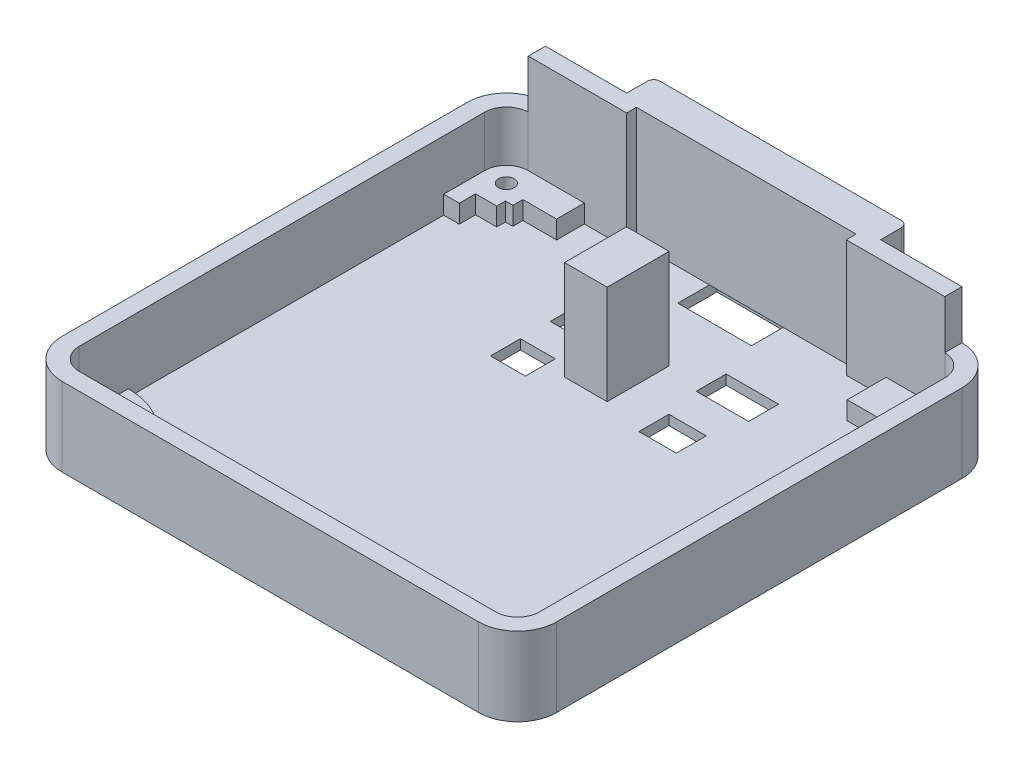
SolidWorks part; units mm, degrees
ref_plane "Front Plane" through (0, 0, 0) normal (0, 0, 1) x (1, 0, 0)
ref_plane "Top Plane" through (0, 0, 0) normal (0, 1, 0) x (1, 0, 0)
ref_plane "Right Plane" through (0, 0, 0) normal (1, 0, 0) x (0, 0, -1)
sketch "Sketch2" plane through (0, 0, 0) normal (0, 1, 0) x (1, 0, 0)
  line L6 (-46.8585, -41.275) -> (-46.8585, 41.275)
  line L8 (46.8585, -41.275) -> (46.8585, 41.275)
  line L9 (42.418, -45.7155) -> (-42.418, -45.7155)
  line L10 (-42.418, 45.7155) -> (-16.8754, 45.7155)
  line L11 (-46.8585, -41.275) -> (-50.3585, -41.275)
  line L14 (-50.3585, -41.275) -> (-50.3585, 41.275)
  line L15 (-42.418, 45.7155) -> (-42.418, 49.2155)
  line L16 (-42.418, 41.275) -> (-37.8452, 38.0373)
  line L17 (-42.418, 49.2155) -> (42.418, 49.2155)
  line L18 (-37.8452, 38.0373) -> (-37.8452, 40.0693)
  line L19 (-37.8452, 40.0693) -> (-30.9872, 40.0693)
  line L20 (-30.9872, 40.0693) -> (-30.9872, 45.7155)
  line L21 (-37.8452, 38.0373) -> (-39.3692, 38.0373)
  line L22 (46.8585, 41.275) -> (50.3585, 41.275)
  line L23 (42.418, -45.7155) -> (42.418, -49.2155)
  line L24 (-39.3692, 38.0373) -> (-39.3692, 36.2593)
  line L25 (42.418, -49.2155) -> (-42.418, -49.2155)
  line L26 (-39.3692, 36.2593) -> (-43.6872, 36.2593)
  line L27 (-43.6872, 36.2593) -> (-43.6872, 32.9573)
  line L28 (50.3585, 41.275) -> (50.3585, -41.275)
  line L34 (-43.6872, 32.9573) -> (-46.8585, 32.9573)
  line L37 (42.418, 41.275) -> (50.0148, 49.9834)
  line L46 (-16.2544, 31.1733) -> (-10.1584, 31.1733)
  line L52 (-10.1584, 31.1733) -> (-10.1584, 25.0773)
  line L58 (-10.1584, 25.0773) -> (-17.2704, 25.0773)
  line L64 (-17.2704, 25.0773) -> (-17.2704, 31.1733)
  line L70 (-17.2704, 31.1733) -> (-16.2544, 31.1733)
  line L76 (-17.2704, 25.0773) -> (-17.2704, 18.9813)
  line L82 (-17.2704, 18.9813) -> (-10.1584, 18.9813)
  line L88 (-10.1584, 18.9813) -> (-10.1584, 12.8853)
  line L94 (-10.1584, 12.8853) -> (-17.2704, 12.8853)
  line L100 (-17.2704, 12.8853) -> (-17.2704, 18.9813)
  line L111 (22.418, 45.7155) -> (42.418, 45.7155)
  line L112 (-10.1584, 31.1733) -> (9.9076, 31.1733)
  line L113 (9.9076, 31.1733) -> (9.9076, 33.7133)
  line L114 (9.9076, 33.7133) -> (20.5756, 33.7133)
  line L115 (20.5756, 33.7133) -> (20.5756, 27.6173)
  line L116 (20.5756, 27.6173) -> (9.9076, 27.6173)
  line L117 (9.9076, 27.6173) -> (9.9076, 31.1733)
  line L118 (9.9076, 27.6173) -> (9.9076, 20.7633)
  line L119 (9.9076, 20.7633) -> (18.7976, 20.7633)
  line L120 (18.7976, 20.7633) -> (18.7976, 14.6673)
  line L121 (18.7976, 14.6673) -> (11.1776, 14.6673)
  line L122 (11.1776, 14.6673) -> (11.1776, 20.7633)
  line L123 (42.418, 41.275) -> (0, 41.275)
  line L124 (42.418, 41.275) -> (39.3704, 37.7815)
  line L125 (39.3704, 37.7815) -> (39.3704, 33.2095)
  line L126 (39.3704, 37.7815) -> (30.4804, 37.7815)
  line L127 (30.4804, 37.7815) -> (30.4804, 45.7155)
  line L128 (39.3704, 33.2095) -> (46.8585, 33.2095)
  line L129 (22.418, 45.7155) -> (-16.8754, 45.7155)
  line L130 (46.8585, -41.275) -> (46.8585, -31.275)
  line L131 (42.418, -45.7155) -> (32.418, -45.7155)
  line L132 (-42.418, -45.7155) -> (-32.418, -45.7155)
  line L133 (-46.8585, -41.275) -> (-46.8585, -31.275)
  arc A0 (-42.418, 45.7155) -> (-46.8585, 41.275) centre (-42.418, 41.275) ccw
  arc A1 (42.418, 45.7155) -> (46.8585, 41.275) centre (42.418, 41.275) cw
  arc A2 (-46.8585, -41.275) -> (-42.418, -45.7155) centre (-42.418, -41.275) ccw
  arc A3 (46.8585, -41.275) -> (42.418, -45.7155) centre (42.418, -41.275) cw
  circle A4 centre (42.418, 41.275) radius 1.6
  circle A5 centre (-42.418, 41.275) radius 1.6
  circle A6 centre (-42.418, -41.275) radius 1.6
  circle A7 centre (42.418, -41.275) radius 1.6
  arc A8 (-42.418, 49.2155) -> (-50.3585, 41.275) centre (-42.418, 41.275) ccw
  arc A9 (42.418, 49.2155) -> (50.3585, 41.275) centre (42.418, 41.275) cw
  arc A10 (42.418, -49.2155) -> (50.3585, -41.275) centre (42.418, -41.275) ccw
  arc A11 (-42.418, -49.2155) -> (-50.3585, -41.275) centre (-42.418, -41.275) cw
  arc A12 (46.8585, -31.275) -> (32.418, -45.7155) centre (46.8585, -45.7155) ccw
  arc A13 (-46.8585, -31.275) -> (-32.418, -45.7155) centre (-46.8585, -45.7155) cw
extrude "Boss-Extrude1" add sketch "Sketch2" along normal blind 1.5 contours L8 A12 L9 A3 A7 | A13 L6 A2 L9 A6 region at (-40.4967, 0, 39.3537) region at (40.4967, 0, 39.3537)
sketch "Sketch5" plane through (0, 0, 0) normal (0, -1, 0) x (1, 0, 0)
  line L0 (-17.2704, -25.0773) -> (-17.2704, -18.9813) construction
  line L1 (42.418, -41.275) -> (50.0148, -49.9834) construction
  line L2 (42.418, -41.275) -> (0, -41.275) construction
  line L3 (42.418, -41.275) -> (39.3704, -37.7815) construction
  line L4 (-42.418, -41.275) -> (-37.8452, -38.0373) construction
  line L5 (-42.418, -45.7155) -> (-16.8754, -45.7155) construction
  line L6 (22.418, -45.7155) -> (-16.8754, -45.7155) construction
  line L7 (22.418, -45.7155) -> (42.418, -45.7155) construction
  line L8 (-42.418, -45.7155) -> (-42.418, -49.2155) construction
  line L9 (-46.8585, 41.275) -> (-46.8585, -41.275) construction
  line L10 (42.418, 45.7155) -> (-42.418, 45.7155) construction
  line L11 (-42.418, 45.7155) -> (-32.418, 45.7155) construction
  line L12 (-46.8585, 41.275) -> (-46.8585, 31.275) construction
  line L13 (42.418, 45.7155) -> (42.418, 49.2155) construction
  line L14 (46.8585, 41.275) -> (46.8585, 31.275) construction
  line L15 (42.418, 45.7155) -> (32.418, 45.7155) construction
  line L16 (46.8585, 41.275) -> (46.8585, -41.275) construction
  line L17 (46.8585, -41.275) -> (50.3585, -41.275) construction
  line L18 (-46.8585, 41.275) -> (-50.3585, 41.275) construction
  line L19 (-37.8452, -38.0373) -> (-39.3692, -38.0373) construction
  line L20 (-39.3692, -38.0373) -> (-39.3692, -36.2593) construction
  line L21 (-39.3692, -36.2593) -> (-43.6872, -36.2593) construction
  line L22 (-43.6872, -36.2593) -> (-43.6872, -32.9573) construction
  line L23 (-43.6872, -32.9573) -> (-46.8585, -32.9573) construction
  line L24 (-37.8452, -38.0373) -> (-37.8452, -40.0693) construction
  line L25 (-37.8452, -40.0693) -> (-30.9872, -40.0693) construction
  line L26 (-30.9872, -40.0693) -> (-30.9872, -45.7155) construction
  line L27 (-42.418, -49.2155) -> (42.418, -49.2155) construction
  line L28 (-50.3585, 41.275) -> (-50.3585, -41.275) construction
  line L29 (42.418, 49.2155) -> (-42.418, 49.2155) construction
  line L30 (9.9076, -31.1733) -> (9.9076, -33.7133) construction
  line L31 (9.9076, -33.7133) -> (20.5756, -33.7133) construction
  line L32 (20.5756, -33.7133) -> (20.5756, -27.6173) construction
  line L33 (20.5756, -27.6173) -> (9.9076, -27.6173) construction
  line L34 (9.9076, -27.6173) -> (9.9076, -31.1733) construction
  line L35 (9.9076, -27.6173) -> (9.9076, -20.7633) construction
  line L36 (9.9076, -20.7633) -> (18.7976, -20.7633) construction
  line L37 (18.7976, -20.7633) -> (18.7976, -14.6673) construction
  line L38 (18.7976, -14.6673) -> (11.1776, -14.6673) construction
  line L39 (11.1776, -14.6673) -> (11.1776, -20.7633) construction
  line L40 (-10.1584, -31.1733) -> (9.9076, -31.1733) construction
  line L41 (50.3585, -41.275) -> (50.3585, 41.275) construction
  line L42 (39.3704, -37.7815) -> (39.3704, -33.2095) construction
  line L43 (39.3704, -33.2095) -> (46.8585, -33.2095) construction
  line L44 (39.3704, -37.7815) -> (30.4804, -37.7815) construction
  line L45 (30.4804, -37.7815) -> (30.4804, -45.7155) construction
  line L46 (-10.1584, -31.1733) -> (-10.1584, -25.0773) construction
  line L47 (-10.1584, -25.0773) -> (-17.2704, -25.0773) construction
  line L48 (-16.2544, -31.1733) -> (-10.1584, -31.1733) construction
  line L49 (-17.2704, -31.1733) -> (-16.2544, -31.1733) construction
  line L50 (-17.2704, -25.0773) -> (-17.2704, -31.1733) construction
  line L51 (-17.2704, -18.9813) -> (-10.1584, -18.9813) construction
  line L52 (-10.1584, -18.9813) -> (-10.1584, -12.8853) construction
  line L53 (-10.1584, -12.8853) -> (-17.2704, -12.8853) construction
  line L54 (-17.2704, -12.8853) -> (-17.2704, -18.9813) construction
  line L55 (-17.2704, -25.0773) -> (-17.2704, -18.9813)
  line L56 (42.418, -41.275) -> (50.0148, -49.9834)
  line L57 (42.418, -41.275) -> (0, -41.275)
  line L58 (42.418, -41.275) -> (39.3704, -37.7815)
  line L59 (-42.418, -41.275) -> (-37.8452, -38.0373)
  line L60 (-42.418, -45.7155) -> (-16.8754, -45.7155)
  line L61 (22.418, -45.7155) -> (-16.8754, -45.7155)
  line L62 (22.418, -45.7155) -> (42.418, -45.7155)
  line L63 (-42.418, -45.7155) -> (-42.418, -49.2155)
  line L64 (-46.8585, 41.275) -> (-46.8585, -41.275)
  line L65 (42.418, 45.7155) -> (-42.418, 45.7155)
  line L66 (-42.418, 45.7155) -> (-32.418, 45.7155)
  line L67 (-46.8585, 41.275) -> (-46.8585, 31.275)
  line L68 (42.418, 45.7155) -> (42.418, 49.2155)
  line L69 (46.8585, 41.275) -> (46.8585, 31.275)
  line L70 (42.418, 45.7155) -> (32.418, 45.7155)
  line L71 (46.8585, 41.275) -> (46.8585, -41.275)
  line L72 (46.8585, -41.275) -> (50.3585, -41.275)
  line L73 (-46.8585, 41.275) -> (-50.3585, 41.275)
  line L74 (-37.8452, -38.0373) -> (-39.3692, -38.0373)
  line L75 (-39.3692, -38.0373) -> (-39.3692, -36.2593)
  line L76 (-39.3692, -36.2593) -> (-43.6872, -36.2593)
  line L77 (-43.6872, -36.2593) -> (-43.6872, -32.9573)
  line L78 (-43.6872, -32.9573) -> (-46.8585, -32.9573)
  line L79 (-37.8452, -38.0373) -> (-37.8452, -40.0693)
  line L80 (-37.8452, -40.0693) -> (-30.9872, -40.0693)
  line L81 (-30.9872, -40.0693) -> (-30.9872, -45.7155)
  line L82 (-42.418, -49.2155) -> (42.418, -49.2155)
  line L83 (-50.3585, 41.275) -> (-50.3585, -41.275)
  line L84 (42.418, 49.2155) -> (-42.418, 49.2155)
  line L85 (9.9076, -31.1733) -> (9.9076, -33.7133)
  line L86 (9.9076, -33.7133) -> (20.5756, -33.7133)
  line L87 (20.5756, -33.7133) -> (20.5756, -27.6173)
  line L88 (20.5756, -27.6173) -> (9.9076, -27.6173)
  line L89 (9.9076, -27.6173) -> (9.9076, -31.1733)
  line L90 (9.9076, -27.6173) -> (9.9076, -20.7633)
  line L91 (9.9076, -20.7633) -> (18.7976, -20.7633)
  line L92 (18.7976, -20.7633) -> (18.7976, -14.6673)
  line L93 (18.7976, -14.6673) -> (11.1776, -14.6673)
  line L94 (11.1776, -14.6673) -> (11.1776, -20.7633)
  line L95 (-10.1584, -31.1733) -> (9.9076, -31.1733)
  line L96 (50.3585, -41.275) -> (50.3585, 41.275)
  line L97 (39.3704, -37.7815) -> (39.3704, -33.2095)
  line L98 (39.3704, -33.2095) -> (46.8585, -33.2095)
  line L99 (39.3704, -37.7815) -> (30.4804, -37.7815)
  line L100 (30.4804, -37.7815) -> (30.4804, -45.7155)
  line L101 (-10.1584, -31.1733) -> (-10.1584, -25.0773)
  line L102 (-10.1584, -25.0773) -> (-17.2704, -25.0773)
  line L103 (-16.2544, -31.1733) -> (-10.1584, -31.1733)
  line L104 (-17.2704, -31.1733) -> (-16.2544, -31.1733)
  line L105 (-17.2704, -25.0773) -> (-17.2704, -31.1733)
  line L106 (-17.2704, -18.9813) -> (-10.1584, -18.9813)
  line L107 (-10.1584, -18.9813) -> (-10.1584, -12.8853)
  line L108 (-10.1584, -12.8853) -> (-17.2704, -12.8853)
  line L109 (-17.2704, -12.8853) -> (-17.2704, -18.9813)
  line L110 (50.3585, -41.275) -> (50.3585, 41.275)
  line L111 (42.418, 49.2155) -> (-42.418, 49.2155)
  line L112 (-50.3585, 41.275) -> (-50.3585, -41.275)
  line L113 (-42.418, -49.2155) -> (42.418, -49.2155)
  arc A0 (42.418, -45.7155) -> (46.8585, -41.275) centre (42.418, -41.275) ccw construction
  arc A1 (-46.8585, -41.275) -> (-42.418, -45.7155) centre (-42.418, -41.275) ccw construction
  arc A2 (-46.8585, 31.275) -> (-32.418, 45.7155) centre (-46.8585, 45.7155) ccw construction
  arc A3 (-42.418, 45.7155) -> (-46.8585, 41.275) centre (-42.418, 41.275) ccw construction
  arc A4 (32.418, 45.7155) -> (46.8585, 31.275) centre (46.8585, 45.7155) ccw construction
  arc A5 (46.8585, 41.275) -> (42.418, 45.7155) centre (42.418, 41.275) ccw construction
  arc A6 (42.418, -49.2155) -> (50.3585, -41.275) centre (42.418, -41.275) ccw construction
  arc A7 (-50.3585, -41.275) -> (-42.418, -49.2155) centre (-42.418, -41.275) ccw construction
  arc A8 (-42.418, 49.2155) -> (-50.3585, 41.275) centre (-42.418, 41.275) ccw construction
  arc A9 (50.3585, 41.275) -> (42.418, 49.2155) centre (42.418, 41.275) ccw construction
  circle A10 centre (42.418, 41.275) radius 1.6 construction
  circle A11 centre (-42.418, 41.275) radius 1.6 construction
  circle A12 centre (-42.418, -41.275) radius 1.6 construction
  circle A13 centre (42.418, -41.275) radius 1.6 construction
  arc A14 (42.418, -45.7155) -> (46.8585, -41.275) centre (42.418, -41.275) ccw
  arc A15 (-46.8585, -41.275) -> (-42.418, -45.7155) centre (-42.418, -41.275) ccw
  arc A16 (-46.8585, 31.275) -> (-32.418, 45.7155) centre (-46.8585, 45.7155) ccw
  arc A17 (-42.418, 45.7155) -> (-46.8585, 41.275) centre (-42.418, 41.275) ccw
  arc A18 (32.418, 45.7155) -> (46.8585, 31.275) centre (46.8585, 45.7155) ccw
  arc A19 (46.8585, 41.275) -> (42.418, 45.7155) centre (42.418, 41.275) ccw
  arc A20 (42.418, -49.2155) -> (50.3585, -41.275) centre (42.418, -41.275) ccw
  arc A21 (-50.3585, -41.275) -> (-42.418, -49.2155) centre (-42.418, -41.275) ccw
  arc A22 (-42.418, 49.2155) -> (-50.3585, 41.275) centre (-42.418, 41.275) ccw
  arc A23 (50.3585, 41.275) -> (42.418, 49.2155) centre (42.418, 41.275) ccw
  circle A24 centre (42.418, 41.275) radius 1.6
  circle A25 centre (-42.418, 41.275) radius 1.6
  circle A26 centre (-42.418, -41.275) radius 1.6
  circle A27 centre (42.418, -41.275) radius 1.6
  arc A28 (42.418, -49.2155) -> (50.3585, -41.275) centre (42.418, -41.275) ccw
  arc A29 (50.3585, 41.275) -> (42.418, 49.2155) centre (42.418, 41.275) ccw
  arc A30 (-42.418, 49.2155) -> (-50.3585, 41.275) centre (-42.418, 41.275) ccw
  arc A31 (-50.3585, -41.275) -> (-42.418, -49.2155) centre (-42.418, -41.275) ccw
  arc M1 (-46.8585, 31.275) -> (-32.418, 45.7155) centre (-46.8585, 45.7155) ccw
  line M2 (-32.418, 45.7155) -> (-42.418, 45.7155)
  arc M3 (-42.418, 45.7155) -> (-46.8585, 41.275) centre (-42.418, 41.275) ccw
  line M4 (-46.8585, 41.275) -> (-46.8585, 31.275)
  circle M5 centre (-42.418, 41.275) radius 1.6
extrude "Boss-Extrude3" add sketch "Sketch5" along normal blind 2 contours L82 A20 L56 A14 L62 L61 L60 L63 | L56 A20 L72 A14 | L96 A23 L68 A19 L69 L71 L72 | A18 L65 L64 L78 L77 L76 L75 L74 L79 L80 L81 L60 L61 L62 L100 L99 L97 L98 L71 L109 L108 L107 L106 L102 L101 L89 L94 L93 L92 L91 L88 L87 L86 L85 L103 L104 L105 M1 | A27 L58 L99 L100 L57 | A27 L57 L100 L62 A14 L56 | A27 L56 A14 L71 L98 L97 L58 | A26 L74 L75 L76 L77 L78 L64 A15 L60 L81 L80 L79 | M4 M1 M2 M3 M5 | L69 A19 L65 A18 A24 | L84 A22 L73 L65 L68 M3 M2 | L83 A21 L63 A15 L64 L73 M4 region at (43.6425, 0, -37.4818) region at (37.0258, 0, -43.6304) region at (35.5464, 0, -39.5753) region at (48.0295, 0, -43.8264) region at (2.2185, 0, -47.4473) region at (-0.2178, 0, 0.4927) region at (48.3825, 0, 4.776) region at (-48.3825, 0, -4.776) region at (40.4967, 0, 39.3537) region at (-39.9913, 0, -40.9811) region at (-4.7781, 0, 47.245) region at (-40.4967, 0, 39.3537)
sketch "Sketch6" plane through (0, 0, 0) normal (0, 1, 0) x (1, 0, 0)
  line L0 (-17.2704, 25.0773) -> (-17.2704, 18.9813) construction
  line L1 (42.418, 41.275) -> (50.0148, 49.9834) construction
  line L2 (42.418, 41.275) -> (0, 41.275) construction
  line L3 (42.418, 41.275) -> (39.3704, 37.7815) construction
  line L4 (-42.418, 41.275) -> (-37.8452, 38.0373) construction
  line L5 (-42.418, 45.7155) -> (-16.8754, 45.7155) construction
  line L6 (22.418, 45.7155) -> (-16.8754, 45.7155) construction
  line L7 (22.418, 45.7155) -> (42.418, 45.7155) construction
  line L8 (-42.418, 45.7155) -> (-42.418, 49.2155) construction
  line L9 (-46.8585, -41.275) -> (-46.8585, 41.275) construction
  line L10 (42.418, -45.7155) -> (-42.418, -45.7155) construction
  line L11 (-42.418, -45.7155) -> (-32.418, -45.7155) construction
  line L12 (-46.8585, -41.275) -> (-46.8585, -31.275) construction
  line L13 (42.418, -45.7155) -> (42.418, -49.2155) construction
  line L14 (46.8585, -41.275) -> (46.8585, -31.275) construction
  line L15 (42.418, -45.7155) -> (32.418, -45.7155) construction
  line L16 (46.8585, -41.275) -> (46.8585, 41.275) construction
  line L17 (46.8585, 41.275) -> (50.3585, 41.275) construction
  line L18 (-46.8585, -41.275) -> (-50.3585, -41.275) construction
  line L19 (-37.8452, 38.0373) -> (-39.3692, 38.0373) construction
  line L20 (-39.3692, 38.0373) -> (-39.3692, 36.2593) construction
  line L21 (-39.3692, 36.2593) -> (-43.6872, 36.2593) construction
  line L22 (-43.6872, 36.2593) -> (-43.6872, 32.9573) construction
  line L23 (-43.6872, 32.9573) -> (-46.8585, 32.9573) construction
  line L24 (-37.8452, 38.0373) -> (-37.8452, 40.0693) construction
  line L25 (-37.8452, 40.0693) -> (-30.9872, 40.0693) construction
  line L26 (-30.9872, 40.0693) -> (-30.9872, 45.7155) construction
  line L27 (-42.418, 49.2155) -> (42.418, 49.2155) construction
  line L28 (-50.3585, -41.275) -> (-50.3585, 41.275) construction
  line L29 (42.418, -49.2155) -> (-42.418, -49.2155) construction
  line L30 (9.9076, 31.1733) -> (9.9076, 33.7133) construction
  line L31 (9.9076, 33.7133) -> (20.5756, 33.7133) construction
  line L32 (20.5756, 33.7133) -> (20.5756, 27.6173) construction
  line L33 (20.5756, 27.6173) -> (9.9076, 27.6173) construction
  line L34 (9.9076, 27.6173) -> (9.9076, 31.1733) construction
  line L35 (9.9076, 27.6173) -> (9.9076, 20.7633) construction
  line L36 (9.9076, 20.7633) -> (18.7976, 20.7633) construction
  line L37 (18.7976, 20.7633) -> (18.7976, 14.6673) construction
  line L38 (18.7976, 14.6673) -> (11.1776, 14.6673) construction
  line L39 (11.1776, 14.6673) -> (11.1776, 20.7633) construction
  line L40 (-10.1584, 31.1733) -> (9.9076, 31.1733) construction
  line L41 (50.3585, 41.275) -> (50.3585, -41.275) construction
  line L42 (39.3704, 37.7815) -> (39.3704, 33.2095) construction
  line L43 (39.3704, 33.2095) -> (46.8585, 33.2095) construction
  line L44 (39.3704, 37.7815) -> (30.4804, 37.7815) construction
  line L45 (30.4804, 37.7815) -> (30.4804, 45.7155) construction
  line L46 (-10.1584, 31.1733) -> (-10.1584, 25.0773) construction
  line L47 (-10.1584, 25.0773) -> (-17.2704, 25.0773) construction
  line L48 (-16.2544, 31.1733) -> (-10.1584, 31.1733) construction
  line L49 (-17.2704, 31.1733) -> (-16.2544, 31.1733) construction
  line L50 (-17.2704, 25.0773) -> (-17.2704, 31.1733) construction
  line L51 (-17.2704, 18.9813) -> (-10.1584, 18.9813) construction
  line L52 (-10.1584, 18.9813) -> (-10.1584, 12.8853) construction
  line L53 (-10.1584, 12.8853) -> (-17.2704, 12.8853) construction
  line L54 (-17.2704, 12.8853) -> (-17.2704, 18.9813) construction
  line L55 (-17.2704, 25.0773) -> (-17.2704, 18.9813)
  line L56 (42.418, 41.275) -> (50.0148, 49.9834)
  line L57 (42.418, 41.275) -> (0, 41.275)
  line L58 (42.418, 41.275) -> (39.3704, 37.7815)
  line L59 (-42.418, 41.275) -> (-37.8452, 38.0373)
  line L60 (-42.418, 45.7155) -> (-16.8754, 45.7155)
  line L61 (22.418, 45.7155) -> (-16.8754, 45.7155)
  line L62 (22.418, 45.7155) -> (42.418, 45.7155)
  line L63 (-42.418, 45.7155) -> (-42.418, 49.2155)
  line L64 (-46.8585, -41.275) -> (-46.8585, 41.275)
  line L65 (42.418, -45.7155) -> (-42.418, -45.7155)
  line L66 (-42.418, -45.7155) -> (-32.418, -45.7155)
  line L67 (-46.8585, -41.275) -> (-46.8585, -31.275)
  line L68 (42.418, -45.7155) -> (42.418, -49.2155)
  line L69 (46.8585, -41.275) -> (46.8585, -31.275)
  line L70 (42.418, -45.7155) -> (32.418, -45.7155)
  line L71 (46.8585, -41.275) -> (46.8585, 41.275)
  line L72 (46.8585, 41.275) -> (50.3585, 41.275)
  line L73 (-46.8585, -41.275) -> (-50.3585, -41.275)
  line L74 (-37.8452, 38.0373) -> (-39.3692, 38.0373)
  line L75 (-39.3692, 38.0373) -> (-39.3692, 36.2593)
  line L76 (-39.3692, 36.2593) -> (-43.6872, 36.2593)
  line L77 (-43.6872, 36.2593) -> (-43.6872, 32.9573)
  line L78 (-43.6872, 32.9573) -> (-46.8585, 32.9573)
  line L79 (-37.8452, 38.0373) -> (-37.8452, 40.0693)
  line L80 (-37.8452, 40.0693) -> (-30.9872, 40.0693)
  line L81 (-30.9872, 40.0693) -> (-30.9872, 45.7155)
  line L82 (-42.418, 49.2155) -> (42.418, 49.2155)
  line L83 (-50.3585, -41.275) -> (-50.3585, 41.275)
  line L84 (42.418, -49.2155) -> (-42.418, -49.2155)
  line L85 (9.9076, 31.1733) -> (9.9076, 33.7133)
  line L86 (9.9076, 33.7133) -> (20.5756, 33.7133)
  line L87 (20.5756, 33.7133) -> (20.5756, 27.6173)
  line L88 (20.5756, 27.6173) -> (9.9076, 27.6173)
  line L89 (9.9076, 27.6173) -> (9.9076, 31.1733)
  line L90 (9.9076, 27.6173) -> (9.9076, 20.7633)
  line L91 (9.9076, 20.7633) -> (18.7976, 20.7633)
  line L92 (18.7976, 20.7633) -> (18.7976, 14.6673)
  line L93 (18.7976, 14.6673) -> (11.1776, 14.6673)
  line L94 (11.1776, 14.6673) -> (11.1776, 20.7633)
  line L95 (-10.1584, 31.1733) -> (9.9076, 31.1733)
  line L96 (50.3585, 41.275) -> (50.3585, -41.275)
  line L97 (39.3704, 37.7815) -> (39.3704, 33.2095)
  line L98 (39.3704, 33.2095) -> (46.8585, 33.2095)
  line L99 (39.3704, 37.7815) -> (30.4804, 37.7815)
  line L100 (30.4804, 37.7815) -> (30.4804, 45.7155)
  line L101 (-10.1584, 31.1733) -> (-10.1584, 25.0773)
  line L102 (-10.1584, 25.0773) -> (-17.2704, 25.0773)
  line L103 (-16.2544, 31.1733) -> (-10.1584, 31.1733)
  line L104 (-17.2704, 31.1733) -> (-16.2544, 31.1733)
  line L105 (-17.2704, 25.0773) -> (-17.2704, 31.1733)
  line L106 (-17.2704, 18.9813) -> (-10.1584, 18.9813)
  line L107 (-10.1584, 18.9813) -> (-10.1584, 12.8853)
  line L108 (-10.1584, 12.8853) -> (-17.2704, 12.8853)
  line L109 (-17.2704, 12.8853) -> (-17.2704, 18.9813)
  line L110 (30.4804, 45.7155) -> (30.4804, 37.7815)
  line L111 (39.3704, 37.7815) -> (39.3704, 33.2095)
  line L112 (30.4804, 37.7815) -> (39.3704, 37.7815)
  line L113 (39.3704, 33.2095) -> (46.8585, 33.2095)
  line L114 (46.8585, 33.2095) -> (46.8585, 41.275)
  line L115 (42.418, 45.7155) -> (30.4804, 45.7155)
  line L116 (-42.418, 45.7155) -> (-30.9872, 45.7155)
  line L117 (-30.9872, 45.7155) -> (-30.9872, 40.0693)
  line L118 (-30.9872, 40.0693) -> (-37.8452, 40.0693)
  line L119 (-37.8452, 40.0693) -> (-37.8452, 38.0373)
  line L120 (-37.8452, 38.0373) -> (-39.3692, 38.0373)
  line L121 (-39.3692, 38.0373) -> (-39.3692, 36.2593)
  line L122 (-39.3692, 36.2593) -> (-43.6872, 36.2593)
  line L123 (-43.6872, 36.2593) -> (-43.6872, 32.9573)
  line L124 (-43.6872, 32.9573) -> (-46.8585, 32.9573)
  line L125 (-46.8585, 32.9573) -> (-46.8585, 41.275)
  arc A0 (46.8585, 41.275) -> (42.418, 45.7155) centre (42.418, 41.275) ccw construction
  arc A1 (-42.418, 45.7155) -> (-46.8585, 41.275) centre (-42.418, 41.275) ccw construction
  arc A2 (-32.418, -45.7155) -> (-46.8585, -31.275) centre (-46.8585, -45.7155) ccw construction
  arc A3 (-46.8585, -41.275) -> (-42.418, -45.7155) centre (-42.418, -41.275) ccw construction
  arc A4 (46.8585, -31.275) -> (32.418, -45.7155) centre (46.8585, -45.7155) ccw construction
  arc A5 (42.418, -45.7155) -> (46.8585, -41.275) centre (42.418, -41.275) ccw construction
  arc A6 (50.3585, 41.275) -> (42.418, 49.2155) centre (42.418, 41.275) ccw construction
  arc A7 (-42.418, 49.2155) -> (-50.3585, 41.275) centre (-42.418, 41.275) ccw construction
  arc A8 (-50.3585, -41.275) -> (-42.418, -49.2155) centre (-42.418, -41.275) ccw construction
  arc A9 (42.418, -49.2155) -> (50.3585, -41.275) centre (42.418, -41.275) ccw construction
  circle A10 centre (42.418, -41.275) radius 1.6 construction
  circle A11 centre (-42.418, -41.275) radius 1.6 construction
  circle A12 centre (-42.418, 41.275) radius 1.6 construction
  circle A13 centre (42.418, 41.275) radius 1.6 construction
  arc A14 (46.8585, 41.275) -> (42.418, 45.7155) centre (42.418, 41.275) ccw
  arc A15 (-42.418, 45.7155) -> (-46.8585, 41.275) centre (-42.418, 41.275) ccw
  arc A16 (-32.418, -45.7155) -> (-46.8585, -31.275) centre (-46.8585, -45.7155) ccw
  arc A17 (-46.8585, -41.275) -> (-42.418, -45.7155) centre (-42.418, -41.275) ccw
  arc A18 (46.8585, -31.275) -> (32.418, -45.7155) centre (46.8585, -45.7155) ccw
  arc A19 (42.418, -45.7155) -> (46.8585, -41.275) centre (42.418, -41.275) ccw
  arc A20 (50.3585, 41.275) -> (42.418, 49.2155) centre (42.418, 41.275) ccw
  arc A21 (-42.418, 49.2155) -> (-50.3585, 41.275) centre (-42.418, 41.275) ccw
  arc A22 (-50.3585, -41.275) -> (-42.418, -49.2155) centre (-42.418, -41.275) ccw
  arc A23 (42.418, -49.2155) -> (50.3585, -41.275) centre (42.418, -41.275) ccw
  circle A24 centre (42.418, -41.275) radius 1.6
  circle A25 centre (-42.418, -41.275) radius 1.6
  circle A26 centre (-42.418, 41.275) radius 1.6
  circle A27 centre (42.418, 41.275) radius 1.6
  arc A28 (-46.8585, 41.275) -> (-42.418, 45.7155) centre (-42.418, 41.275) cw
  arc A29 (46.8585, 41.275) -> (42.418, 45.7155) centre (42.418, 41.275) ccw
  circle M17 centre (42.418, 41.275) radius 1.6
  circle M34 centre (-42.418, 41.275) radius 1.6
extrude "Boss-Extrude4" add sketch "Sketch6" along normal blind 3.7 contours L56 A14 L62 L100 L57 M17 | L100 L99 L58 L57 M17 | L71 A14 L56 L58 L97 L98 M17 | L60 A15 L64 L78 L77 L76 L75 L74 L79 L80 L81 M34 region at (37.0258, 0, -43.6304) region at (43.6425, 0, -37.4818) region at (35.5464, 0, -39.5753) region at (-39.9913, 0, -40.9811)
sketch "Sketch7" plane through (0, 0, 0) normal (0, 1, 0) x (1, 0, 0)
  line L0 (-17.2704, 25.0773) -> (-17.2704, 18.9813) construction
  line L1 (42.418, 41.275) -> (50.0148, 49.9834) construction
  line L2 (42.418, 41.275) -> (0, 41.275) construction
  line L3 (42.418, 41.275) -> (39.3704, 37.7815) construction
  line L4 (-42.418, 41.275) -> (-37.8452, 38.0373) construction
  line L5 (-42.418, 45.7155) -> (-16.8754, 45.7155) construction
  line L6 (22.418, 45.7155) -> (-16.8754, 45.7155) construction
  line L7 (22.418, 45.7155) -> (42.418, 45.7155) construction
  line L8 (-42.418, 45.7155) -> (-42.418, 49.2155) construction
  line L9 (-46.8585, -41.275) -> (-46.8585, 41.275) construction
  line L10 (42.418, -45.7155) -> (-42.418, -45.7155) construction
  line L11 (-42.418, -45.7155) -> (-32.418, -45.7155) construction
  line L12 (-46.8585, -41.275) -> (-46.8585, -31.275) construction
  line L13 (42.418, -45.7155) -> (42.418, -49.2155) construction
  line L14 (46.8585, -41.275) -> (46.8585, -31.275) construction
  line L15 (42.418, -45.7155) -> (32.418, -45.7155) construction
  line L16 (46.8585, -41.275) -> (46.8585, 41.275) construction
  line L17 (46.8585, 41.275) -> (50.3585, 41.275) construction
  line L18 (-46.8585, -41.275) -> (-50.3585, -41.275) construction
  line L19 (-37.8452, 38.0373) -> (-39.3692, 38.0373) construction
  line L20 (-39.3692, 38.0373) -> (-39.3692, 36.2593) construction
  line L21 (-39.3692, 36.2593) -> (-43.6872, 36.2593) construction
  line L22 (-43.6872, 36.2593) -> (-43.6872, 32.9573) construction
  line L23 (-43.6872, 32.9573) -> (-46.8585, 32.9573) construction
  line L24 (-37.8452, 38.0373) -> (-37.8452, 40.0693) construction
  line L25 (-37.8452, 40.0693) -> (-30.9872, 40.0693) construction
  line L26 (-30.9872, 40.0693) -> (-30.9872, 45.7155) construction
  line L27 (-42.418, 49.2155) -> (42.418, 49.2155) construction
  line L28 (-50.3585, -41.275) -> (-50.3585, 41.275) construction
  line L29 (42.418, -49.2155) -> (-42.418, -49.2155) construction
  line L30 (9.9076, 31.1733) -> (9.9076, 33.7133) construction
  line L31 (9.9076, 33.7133) -> (20.5756, 33.7133) construction
  line L32 (20.5756, 33.7133) -> (20.5756, 27.6173) construction
  line L33 (20.5756, 27.6173) -> (9.9076, 27.6173) construction
  line L34 (9.9076, 27.6173) -> (9.9076, 31.1733) construction
  line L35 (9.9076, 27.6173) -> (9.9076, 20.7633) construction
  line L36 (9.9076, 20.7633) -> (18.7976, 20.7633) construction
  line L37 (18.7976, 20.7633) -> (18.7976, 14.6673) construction
  line L38 (18.7976, 14.6673) -> (11.1776, 14.6673) construction
  line L39 (11.1776, 14.6673) -> (11.1776, 20.7633) construction
  line L40 (-10.1584, 31.1733) -> (9.9076, 31.1733) construction
  line L41 (50.3585, 41.275) -> (50.3585, -41.275) construction
  line L42 (39.3704, 37.7815) -> (39.3704, 33.2095) construction
  line L43 (39.3704, 33.2095) -> (46.8585, 33.2095) construction
  line L44 (39.3704, 37.7815) -> (30.4804, 37.7815) construction
  line L45 (30.4804, 37.7815) -> (30.4804, 45.7155) construction
  line L46 (-10.1584, 31.1733) -> (-10.1584, 25.0773) construction
  line L47 (-10.1584, 25.0773) -> (-17.2704, 25.0773) construction
  line L48 (-16.2544, 31.1733) -> (-10.1584, 31.1733) construction
  line L49 (-17.2704, 31.1733) -> (-16.2544, 31.1733) construction
  line L50 (-17.2704, 25.0773) -> (-17.2704, 31.1733) construction
  line L51 (-17.2704, 18.9813) -> (-10.1584, 18.9813) construction
  line L52 (-10.1584, 18.9813) -> (-10.1584, 12.8853) construction
  line L53 (-10.1584, 12.8853) -> (-17.2704, 12.8853) construction
  line L54 (-17.2704, 12.8853) -> (-17.2704, 18.9813) construction
  line L55 (-17.2704, 25.0773) -> (-17.2704, 18.9813)
  line L56 (42.418, 41.275) -> (50.0148, 49.9834)
  line L57 (42.418, 41.275) -> (0, 41.275)
  line L58 (42.418, 41.275) -> (39.3704, 37.7815)
  line L59 (-42.418, 41.275) -> (-37.8452, 38.0373)
  line L60 (-42.418, 45.7155) -> (-16.8754, 45.7155)
  line L61 (22.418, 45.7155) -> (-16.8754, 45.7155)
  line L62 (22.418, 45.7155) -> (42.418, 45.7155)
  line L63 (-42.418, 45.7155) -> (-42.418, 49.2155)
  line L64 (-46.8585, -41.275) -> (-46.8585, 41.275)
  line L65 (42.418, -45.7155) -> (-42.418, -45.7155)
  line L66 (-42.418, -45.7155) -> (-32.418, -45.7155)
  line L67 (-46.8585, -41.275) -> (-46.8585, -31.275)
  line L68 (42.418, -45.7155) -> (42.418, -49.2155)
  line L69 (46.8585, -41.275) -> (46.8585, -31.275)
  line L70 (42.418, -45.7155) -> (32.418, -45.7155)
  line L71 (46.8585, -41.275) -> (46.8585, 41.275)
  line L72 (46.8585, 41.275) -> (50.3585, 41.275)
  line L73 (-46.8585, -41.275) -> (-50.3585, -41.275)
  line L74 (-37.8452, 38.0373) -> (-39.3692, 38.0373)
  line L75 (-39.3692, 38.0373) -> (-39.3692, 36.2593)
  line L76 (-39.3692, 36.2593) -> (-43.6872, 36.2593)
  line L77 (-43.6872, 36.2593) -> (-43.6872, 32.9573)
  line L78 (-43.6872, 32.9573) -> (-46.8585, 32.9573)
  line L79 (-37.8452, 38.0373) -> (-37.8452, 40.0693)
  line L80 (-37.8452, 40.0693) -> (-30.9872, 40.0693)
  line L81 (-30.9872, 40.0693) -> (-30.9872, 45.7155)
  line L82 (-42.418, 49.2155) -> (42.418, 49.2155)
  line L83 (-50.3585, -41.275) -> (-50.3585, 41.275)
  line L84 (42.418, -49.2155) -> (-42.418, -49.2155)
  line L85 (9.9076, 31.1733) -> (9.9076, 33.7133)
  line L86 (9.9076, 33.7133) -> (20.5756, 33.7133)
  line L87 (20.5756, 33.7133) -> (20.5756, 27.6173)
  line L88 (20.5756, 27.6173) -> (9.9076, 27.6173)
  line L89 (9.9076, 27.6173) -> (9.9076, 31.1733)
  line L90 (9.9076, 27.6173) -> (9.9076, 20.7633)
  line L91 (9.9076, 20.7633) -> (18.7976, 20.7633)
  line L92 (18.7976, 20.7633) -> (18.7976, 14.6673)
  line L93 (18.7976, 14.6673) -> (11.1776, 14.6673)
  line L94 (11.1776, 14.6673) -> (11.1776, 20.7633)
  line L95 (-10.1584, 31.1733) -> (9.9076, 31.1733)
  line L96 (50.3585, 41.275) -> (50.3585, -41.275)
  line L97 (39.3704, 37.7815) -> (39.3704, 33.2095)
  line L98 (39.3704, 33.2095) -> (46.8585, 33.2095)
  line L99 (39.3704, 37.7815) -> (30.4804, 37.7815)
  line L100 (30.4804, 37.7815) -> (30.4804, 45.7155)
  line L101 (-10.1584, 31.1733) -> (-10.1584, 25.0773)
  line L102 (-10.1584, 25.0773) -> (-17.2704, 25.0773)
  line L103 (-16.2544, 31.1733) -> (-10.1584, 31.1733)
  line L104 (-17.2704, 31.1733) -> (-16.2544, 31.1733)
  line L105 (-17.2704, 25.0773) -> (-17.2704, 31.1733)
  line L106 (-17.2704, 18.9813) -> (-10.1584, 18.9813)
  line L107 (-10.1584, 18.9813) -> (-10.1584, 12.8853)
  line L108 (-10.1584, 12.8853) -> (-17.2704, 12.8853)
  line L109 (-17.2704, 12.8853) -> (-17.2704, 18.9813)
  line L110 (0, 41.275) -> (-7.5, 41.275)
  line L111 (0, 41.275) -> (7.5, 41.275)
  line L112 (7.5, 41.275) -> (7.5, 49.2155)
  line L113 (-7.5, 41.275) -> (-7.5, 49.2155)
  arc A0 (46.8585, 41.275) -> (42.418, 45.7155) centre (42.418, 41.275) ccw construction
  arc A1 (-42.418, 45.7155) -> (-46.8585, 41.275) centre (-42.418, 41.275) ccw construction
  arc A2 (-32.418, -45.7155) -> (-46.8585, -31.275) centre (-46.8585, -45.7155) ccw construction
  arc A3 (-46.8585, -41.275) -> (-42.418, -45.7155) centre (-42.418, -41.275) ccw construction
  arc A4 (46.8585, -31.275) -> (32.418, -45.7155) centre (46.8585, -45.7155) ccw construction
  arc A5 (42.418, -45.7155) -> (46.8585, -41.275) centre (42.418, -41.275) ccw construction
  arc A6 (50.3585, 41.275) -> (42.418, 49.2155) centre (42.418, 41.275) ccw construction
  arc A7 (-42.418, 49.2155) -> (-50.3585, 41.275) centre (-42.418, 41.275) ccw construction
  arc A8 (-50.3585, -41.275) -> (-42.418, -49.2155) centre (-42.418, -41.275) ccw construction
  arc A9 (42.418, -49.2155) -> (50.3585, -41.275) centre (42.418, -41.275) ccw construction
  circle A10 centre (42.418, -41.275) radius 1.6 construction
  circle A11 centre (-42.418, -41.275) radius 1.6 construction
  circle A12 centre (-42.418, 41.275) radius 1.6 construction
  circle A13 centre (42.418, 41.275) radius 1.6 construction
  arc A14 (46.8585, 41.275) -> (42.418, 45.7155) centre (42.418, 41.275) ccw
  arc A15 (-42.418, 45.7155) -> (-46.8585, 41.275) centre (-42.418, 41.275) ccw
  arc A16 (-32.418, -45.7155) -> (-46.8585, -31.275) centre (-46.8585, -45.7155) ccw
  arc A17 (-46.8585, -41.275) -> (-42.418, -45.7155) centre (-42.418, -41.275) ccw
  arc A18 (46.8585, -31.275) -> (32.418, -45.7155) centre (46.8585, -45.7155) ccw
  arc A19 (42.418, -45.7155) -> (46.8585, -41.275) centre (42.418, -41.275) ccw
  arc A20 (50.3585, 41.275) -> (42.418, 49.2155) centre (42.418, 41.275) ccw
  arc A21 (-42.418, 49.2155) -> (-50.3585, 41.275) centre (-42.418, 41.275) ccw
  arc A22 (-50.3585, -41.275) -> (-42.418, -49.2155) centre (-42.418, -41.275) ccw
  arc A23 (42.418, -49.2155) -> (50.3585, -41.275) centre (42.418, -41.275) ccw
  circle A24 centre (42.418, -41.275) radius 1.6
  circle A25 centre (-42.418, -41.275) radius 1.6
  circle A26 centre (-42.418, 41.275) radius 1.6
  circle A27 centre (42.418, 41.275) radius 1.6
extrude "Cut-Extrude1" cut sketch "Sketch7" against normal blind 18.7 contours L113 L61 L112 L82 | L113 L110 L57 L112 L61 region at (0, 0, -43.4953) region at (0, 0, -47.4655)
sketch "Sketch8" plane through (0, 0, 0) normal (0, 1, 0) x (1, 0, 0)
  line L0 (-17.2704, 25.0773) -> (-17.2704, 18.9813) construction
  line L1 (42.418, 41.275) -> (50.0148, 49.9834) construction
  line L2 (42.418, 41.275) -> (0, 41.275) construction
  line L3 (42.418, 41.275) -> (39.3704, 37.7815) construction
  line L4 (-42.418, 41.275) -> (-37.8452, 38.0373) construction
  line L5 (-42.418, 45.7155) -> (-16.8754, 45.7155) construction
  line L6 (22.418, 45.7155) -> (-16.8754, 45.7155) construction
  line L7 (22.418, 45.7155) -> (42.418, 45.7155) construction
  line L8 (-42.418, 45.7155) -> (-42.418, 49.2155) construction
  line L9 (-46.8585, -41.275) -> (-46.8585, 41.275) construction
  line L10 (42.418, -45.7155) -> (-42.418, -45.7155) construction
  line L11 (-42.418, -45.7155) -> (-32.418, -45.7155) construction
  line L12 (-46.8585, -41.275) -> (-46.8585, -31.275) construction
  line L13 (42.418, -45.7155) -> (42.418, -49.2155) construction
  line L14 (46.8585, -41.275) -> (46.8585, -31.275) construction
  line L15 (42.418, -45.7155) -> (32.418, -45.7155) construction
  line L16 (46.8585, -41.275) -> (46.8585, 41.275) construction
  line L17 (46.8585, 41.275) -> (50.3585, 41.275) construction
  line L18 (-46.8585, -41.275) -> (-50.3585, -41.275) construction
  line L19 (-37.8452, 38.0373) -> (-39.3692, 38.0373) construction
  line L20 (-39.3692, 38.0373) -> (-39.3692, 36.2593) construction
  line L21 (-39.3692, 36.2593) -> (-43.6872, 36.2593) construction
  line L22 (-43.6872, 36.2593) -> (-43.6872, 32.9573) construction
  line L23 (-43.6872, 32.9573) -> (-46.8585, 32.9573) construction
  line L24 (-37.8452, 38.0373) -> (-37.8452, 40.0693) construction
  line L25 (-37.8452, 40.0693) -> (-30.9872, 40.0693) construction
  line L26 (-30.9872, 40.0693) -> (-30.9872, 45.7155) construction
  line L27 (-42.418, 49.2155) -> (42.418, 49.2155) construction
  line L28 (-50.3585, -41.275) -> (-50.3585, 41.275) construction
  line L29 (42.418, -49.2155) -> (-42.418, -49.2155) construction
  line L30 (9.9076, 31.1733) -> (9.9076, 33.7133) construction
  line L31 (9.9076, 33.7133) -> (20.5756, 33.7133) construction
  line L32 (20.5756, 33.7133) -> (20.5756, 27.6173) construction
  line L33 (20.5756, 27.6173) -> (9.9076, 27.6173) construction
  line L34 (9.9076, 27.6173) -> (9.9076, 31.1733) construction
  line L35 (9.9076, 27.6173) -> (9.9076, 20.7633) construction
  line L36 (9.9076, 20.7633) -> (18.7976, 20.7633) construction
  line L37 (18.7976, 20.7633) -> (18.7976, 14.6673) construction
  line L38 (18.7976, 14.6673) -> (11.1776, 14.6673) construction
  line L39 (11.1776, 14.6673) -> (11.1776, 20.7633) construction
  line L40 (-10.1584, 31.1733) -> (9.9076, 31.1733) construction
  line L41 (50.3585, 41.275) -> (50.3585, -41.275) construction
  line L42 (39.3704, 37.7815) -> (39.3704, 33.2095) construction
  line L43 (39.3704, 33.2095) -> (46.8585, 33.2095) construction
  line L44 (39.3704, 37.7815) -> (30.4804, 37.7815) construction
  line L45 (30.4804, 37.7815) -> (30.4804, 45.7155) construction
  line L46 (-10.1584, 31.1733) -> (-10.1584, 25.0773) construction
  line L47 (-10.1584, 25.0773) -> (-17.2704, 25.0773) construction
  line L48 (-16.2544, 31.1733) -> (-10.1584, 31.1733) construction
  line L49 (-17.2704, 31.1733) -> (-16.2544, 31.1733) construction
  line L50 (-17.2704, 25.0773) -> (-17.2704, 31.1733) construction
  line L51 (-17.2704, 18.9813) -> (-10.1584, 18.9813) construction
  line L52 (-10.1584, 18.9813) -> (-10.1584, 12.8853) construction
  line L53 (-10.1584, 12.8853) -> (-17.2704, 12.8853) construction
  line L54 (-17.2704, 12.8853) -> (-17.2704, 18.9813) construction
  line L55 (-17.2704, 25.0773) -> (-17.2704, 18.9813)
  line L56 (42.418, 41.275) -> (50.0148, 49.9834)
  line L57 (42.418, 41.275) -> (0, 41.275)
  line L58 (42.418, 41.275) -> (39.3704, 37.7815)
  line L59 (-42.418, 41.275) -> (-37.8452, 38.0373)
  line L60 (-42.418, 45.7155) -> (-16.8754, 45.7155)
  line L61 (22.418, 45.7155) -> (-16.8754, 45.7155)
  line L62 (22.418, 45.7155) -> (42.418, 45.7155)
  line L63 (-42.418, 45.7155) -> (-42.418, 49.2155)
  line L64 (-46.8585, -41.275) -> (-46.8585, 41.275)
  line L65 (42.418, -45.7155) -> (-42.418, -45.7155)
  line L66 (-42.418, -45.7155) -> (-32.418, -45.7155)
  line L67 (-46.8585, -41.275) -> (-46.8585, -31.275)
  line L68 (42.418, -45.7155) -> (42.418, -49.2155)
  line L69 (46.8585, -41.275) -> (46.8585, -31.275)
  line L70 (42.418, -45.7155) -> (32.418, -45.7155)
  line L71 (46.8585, -41.275) -> (46.8585, 41.275)
  line L72 (46.8585, 41.275) -> (50.3585, 41.275)
  line L73 (-46.8585, -41.275) -> (-50.3585, -41.275)
  line L74 (-37.8452, 38.0373) -> (-39.3692, 38.0373)
  line L75 (-39.3692, 38.0373) -> (-39.3692, 36.2593)
  line L76 (-39.3692, 36.2593) -> (-43.6872, 36.2593)
  line L77 (-43.6872, 36.2593) -> (-43.6872, 32.9573)
  line L78 (-43.6872, 32.9573) -> (-46.8585, 32.9573)
  line L79 (-37.8452, 38.0373) -> (-37.8452, 40.0693)
  line L80 (-37.8452, 40.0693) -> (-30.9872, 40.0693)
  line L81 (-30.9872, 40.0693) -> (-30.9872, 45.7155)
  line L82 (-42.418, 49.2155) -> (42.418, 49.2155)
  line L83 (-50.3585, -41.275) -> (-50.3585, 41.275)
  line L84 (42.418, -49.2155) -> (-42.418, -49.2155)
  line L85 (9.9076, 31.1733) -> (9.9076, 33.7133)
  line L86 (9.9076, 33.7133) -> (20.5756, 33.7133)
  line L87 (20.5756, 33.7133) -> (20.5756, 27.6173)
  line L88 (20.5756, 27.6173) -> (9.9076, 27.6173)
  line L89 (9.9076, 27.6173) -> (9.9076, 31.1733)
  line L90 (9.9076, 27.6173) -> (9.9076, 20.7633)
  line L91 (9.9076, 20.7633) -> (18.7976, 20.7633)
  line L92 (18.7976, 20.7633) -> (18.7976, 14.6673)
  line L93 (18.7976, 14.6673) -> (11.1776, 14.6673)
  line L94 (11.1776, 14.6673) -> (11.1776, 20.7633)
  line L95 (-10.1584, 31.1733) -> (9.9076, 31.1733)
  line L96 (50.3585, 41.275) -> (50.3585, -41.275)
  line L97 (39.3704, 37.7815) -> (39.3704, 33.2095)
  line L98 (39.3704, 33.2095) -> (46.8585, 33.2095)
  line L99 (39.3704, 37.7815) -> (30.4804, 37.7815)
  line L100 (30.4804, 37.7815) -> (30.4804, 45.7155)
  line L101 (-10.1584, 31.1733) -> (-10.1584, 25.0773)
  line L102 (-10.1584, 25.0773) -> (-17.2704, 25.0773)
  line L103 (-16.2544, 31.1733) -> (-10.1584, 31.1733)
  line L104 (-17.2704, 31.1733) -> (-16.2544, 31.1733)
  line L105 (-17.2704, 25.0773) -> (-17.2704, 31.1733)
  line L106 (-17.2704, 18.9813) -> (-10.1584, 18.9813)
  line L107 (-10.1584, 18.9813) -> (-10.1584, 12.8853)
  line L108 (-10.1584, 12.8853) -> (-17.2704, 12.8853)
  line L109 (-17.2704, 12.8853) -> (-17.2704, 18.9813)
  line L110 (-50.3585, -41.275) -> (-50.3585, 41.275)
  line L111 (-42.418, -49.2155) -> (42.418, -49.2155)
  line L112 (50.3585, -41.275) -> (50.3585, 41.275)
  line L113 (42.418, 49.2155) -> (-42.418, 49.2155)
  line L114 (-50.3585, 41.275) -> (-50.3585, -41.275)
  line L115 (-42.418, -45.7155) -> (42.418, -45.7155)
  line L116 (46.8585, -41.275) -> (46.8585, 41.275)
  line L117 (42.418, 45.7155) -> (-42.418, 45.7155)
  line L118 (-46.8585, 41.275) -> (-46.8585, -41.275)
  arc A0 (46.8585, 41.275) -> (42.418, 45.7155) centre (42.418, 41.275) ccw construction
  arc A1 (-42.418, 45.7155) -> (-46.8585, 41.275) centre (-42.418, 41.275) ccw construction
  arc A2 (-32.418, -45.7155) -> (-46.8585, -31.275) centre (-46.8585, -45.7155) ccw construction
  arc A3 (-46.8585, -41.275) -> (-42.418, -45.7155) centre (-42.418, -41.275) ccw construction
  arc A4 (46.8585, -31.275) -> (32.418, -45.7155) centre (46.8585, -45.7155) ccw construction
  arc A5 (42.418, -45.7155) -> (46.8585, -41.275) centre (42.418, -41.275) ccw construction
  arc A6 (50.3585, 41.275) -> (42.418, 49.2155) centre (42.418, 41.275) ccw construction
  arc A7 (-42.418, 49.2155) -> (-50.3585, 41.275) centre (-42.418, 41.275) ccw construction
  arc A8 (-50.3585, -41.275) -> (-42.418, -49.2155) centre (-42.418, -41.275) ccw construction
  arc A9 (42.418, -49.2155) -> (50.3585, -41.275) centre (42.418, -41.275) ccw construction
  circle A10 centre (42.418, -41.275) radius 1.6 construction
  circle A11 centre (-42.418, -41.275) radius 1.6 construction
  circle A12 centre (-42.418, 41.275) radius 1.6 construction
  circle A13 centre (42.418, 41.275) radius 1.6 construction
  arc A14 (46.8585, 41.275) -> (42.418, 45.7155) centre (42.418, 41.275) ccw
  arc A15 (-42.418, 45.7155) -> (-46.8585, 41.275) centre (-42.418, 41.275) ccw
  arc A16 (-32.418, -45.7155) -> (-46.8585, -31.275) centre (-46.8585, -45.7155) ccw
  arc A17 (-46.8585, -41.275) -> (-42.418, -45.7155) centre (-42.418, -41.275) ccw
  arc A18 (46.8585, -31.275) -> (32.418, -45.7155) centre (46.8585, -45.7155) ccw
  arc A19 (42.418, -45.7155) -> (46.8585, -41.275) centre (42.418, -41.275) ccw
  arc A20 (50.3585, 41.275) -> (42.418, 49.2155) centre (42.418, 41.275) ccw
  arc A21 (-42.418, 49.2155) -> (-50.3585, 41.275) centre (-42.418, 41.275) ccw
  arc A22 (-50.3585, -41.275) -> (-42.418, -49.2155) centre (-42.418, -41.275) ccw
  arc A23 (42.418, -49.2155) -> (50.3585, -41.275) centre (42.418, -41.275) ccw
  circle A24 centre (42.418, -41.275) radius 1.6
  circle A25 centre (-42.418, -41.275) radius 1.6
  circle A26 centre (-42.418, 41.275) radius 1.6
  circle A27 centre (42.418, 41.275) radius 1.6
  arc A28 (-46.8585, -41.275) -> (-42.418, -45.7155) centre (-42.418, -41.275) ccw
  arc A29 (42.418, -45.7155) -> (46.8585, -41.275) centre (42.418, -41.275) ccw
  arc A30 (46.8585, 41.275) -> (42.418, 45.7155) centre (42.418, 41.275) ccw
  arc A31 (-42.418, 45.7155) -> (-46.8585, 41.275) centre (-42.418, 41.275) ccw
  arc A32 (-50.3585, -41.275) -> (-42.418, -49.2155) centre (-42.418, -41.275) ccw
  arc A33 (42.418, -49.2155) -> (50.3585, -41.275) centre (42.418, -41.275) ccw
  arc A34 (50.3585, 41.275) -> (42.418, 49.2155) centre (42.418, 41.275) ccw
  arc A35 (-42.418, 49.2155) -> (-50.3585, 41.275) centre (-42.418, 41.275) ccw
extrude "Boss-Extrude5" add sketch "Sketch8" along normal blind 14 contours L63 A21 L83 L73 L64 A15 | L73 A22 L84 L68 L65 A17 | L68 A23 L96 L72 L71 L69 A19 | L56 A20 L82 L63 L60 L61 L62 A14 | L72 A20 L56 A14 region at (2.2185, 0, -47.4473) region at (48.0295, 0, -43.8264) region at (48.3825, 0, 4.776) region at (-48.3825, 0, -4.776) region at (-4.7781, 0, 47.245)
sketch "Sketch10" plane through (0, 3.7, 0) normal (0, 1, 0) x (1, 0, 0)
  line L0 (-2.3026, 25.6216) -> (-2.3026, 13.0008)
  line L1 (-2.3026, 13.0008) -> (6.3735, 13.0008)
  line L2 (6.3735, 13.0008) -> (6.3735, 25.6216)
  line L3 (6.3735, 25.6216) -> (-2.3026, 25.6216)
extrude "Boss-Extrude6" add sketch "Sketch10" along normal blind 20.2 separate body contours L3 L0 L1 L2
sketch "Sketch11" plane through (0, 0, -49.2155) normal (0, 0, -1) x (-1, 0, 0)
  line L8 (-42.418, -2) -> (-7.5, -2)
  line L9 (-7.5, -2) -> (-7.5, 0)
  line L10 (-7.5, 0) -> (7.5, 0)
  line L11 (7.5, 0) -> (7.5, -2)
  line L12 (7.5, -2) -> (42.418, -2)
  line L13 (42.418, -2) -> (42.418, 14)
  line L14 (42.418, 14) -> (-42.418, 14)
  line L15 (-42.418, 14) -> (-42.418, -2)
  line L16 (-42.418, -2) -> (-7.5, -2)
  line L17 (-7.5, -2) -> (-7.5, 0)
  line L18 (-7.5, 0) -> (7.5, 0)
  line L19 (7.5, 0) -> (7.5, -2)
  line L20 (7.5, -2) -> (42.418, -2)
  line L21 (42.418, -2) -> (42.418, 14)
  line L22 (42.418, 14) -> (-42.418, 14)
  line L23 (-42.418, 14) -> (-42.418, -2)
  dimension "D1" = 0
sketch "Sketch13" plane through (0, -2, 0) normal (0, -1, 0) x (1, 0, 0)
  line L0 (46.8585, -33.2095) -> (46.8585, -68.1275)
  line L1 (-46.8585, -32.9573) -> (-46.8585, -74.0554)
  line L2 (42.418, -49.2155) -> (46.8585, -49.2155)
  line L3 (46.8585, -49.2155) -> (25.8585, -49.2155)
  line L4 (-42.418, -49.2155) -> (42.418, -49.2155) construction
  line L5 (-42.418, -49.2155) -> (-21.418, -49.2155)
  line L6 (-20.1364, -54.7155) -> (24.5769, -54.7155)
  line L7 (25.8585, -53.4339) -> (25.8585, -49.2155)
  line L8 (-20.1364, -54.7155) -> (-24.5769, -54.7155)
  line L9 (25.8585, -49.2155) -> (-25.8585, -49.2155)
  line L12 (-25.8585, -53.4339) -> (-25.8585, -49.2155)
  line L15 (-21.418, -49.2155) -> (25.8585, -49.2155)
  line L16 (-42.418, -49.2155) -> (-46.8585, -49.2155)
  line L17 (-46.8585, -49.2155) -> (-25.8585, -49.2155)
  line L20 (-30.9872, -45.7155) -> (-7.5, -45.7155)
  line L21 (-30.9872, -40.0693) -> (-30.9872, -45.7155)
  line L22 (-37.8452, -40.0693) -> (-30.9872, -40.0693)
  line L23 (-37.8452, -38.0373) -> (-37.8452, -40.0693)
  line L24 (-39.3692, -38.0373) -> (-37.8452, -38.0373)
  line L25 (-39.3692, -36.2593) -> (-39.3692, -38.0373)
  line L26 (-43.6872, -36.2593) -> (-39.3692, -36.2593)
  line L27 (-43.6872, -32.9573) -> (-43.6872, -36.2593)
  line L28 (-46.8585, -32.9573) -> (-43.6872, -32.9573)
  line L29 (-46.8585, 31.275) -> (-46.8585, -32.9573)
  line L30 (32.418, 45.7155) -> (-32.418, 45.7155)
  line L31 (46.8585, -33.2095) -> (46.8585, 31.275)
  line L32 (39.3704, -33.2095) -> (46.8585, -33.2095)
  line L33 (39.3704, -37.7815) -> (39.3704, -33.2095)
  line L34 (30.4804, -37.7815) -> (39.3704, -37.7815)
  line L35 (30.4804, -45.7155) -> (30.4804, -37.7815)
  line L36 (7.5, -45.7155) -> (30.4804, -45.7155)
  line L37 (7.5, -41.275) -> (7.5, -45.7155)
  line L38 (-7.5, -41.275) -> (7.5, -41.275)
  line L39 (-7.5, -45.7155) -> (-7.5, -41.275)
  line L40 (-30.9872, -45.7155) -> (-7.5, -45.7155)
  line L41 (-30.9872, -40.0693) -> (-30.9872, -45.7155)
  line L42 (-37.8452, -40.0693) -> (-30.9872, -40.0693)
  line L43 (-37.8452, -38.0373) -> (-37.8452, -40.0693)
  line L44 (-39.3692, -38.0373) -> (-37.8452, -38.0373)
  line L45 (-39.3692, -36.2593) -> (-39.3692, -38.0373)
  line L46 (-43.6872, -36.2593) -> (-39.3692, -36.2593)
  line L47 (-43.6872, -32.9573) -> (-43.6872, -36.2593)
  line L48 (-46.8585, -32.9573) -> (-43.6872, -32.9573)
  line L49 (-46.8585, 31.275) -> (-46.8585, -32.9573)
  line L50 (32.418, 45.7155) -> (-32.418, 45.7155)
  line L51 (46.8585, -33.2095) -> (46.8585, 31.275)
  line L52 (39.3704, -33.2095) -> (46.8585, -33.2095)
  line L53 (39.3704, -37.7815) -> (39.3704, -33.2095)
  line L54 (30.4804, -37.7815) -> (39.3704, -37.7815)
  line L55 (30.4804, -45.7155) -> (30.4804, -37.7815)
  line L56 (7.5, -45.7155) -> (30.4804, -45.7155)
  line L57 (7.5, -41.275) -> (7.5, -45.7155)
  line L58 (-7.5, -41.275) -> (7.5, -41.275)
  line L59 (-7.5, -45.7155) -> (-7.5, -41.275)
  arc A0 (25.8585, -53.4339) -> (24.5769, -54.7155) centre (24.5769, -53.4339) cw
  arc A1 (-25.8585, -53.4339) -> (-24.5769, -54.7155) centre (-24.5769, -53.4339) ccw
  arc A2 (-46.8585, 31.275) -> (-32.418, 45.7155) centre (-46.8585, 45.7155) ccw
  arc A3 (32.418, 45.7155) -> (46.8585, 31.275) centre (46.8585, 45.7155) ccw
  arc A4 (-46.8585, 31.275) -> (-32.418, 45.7155) centre (-46.8585, 45.7155) ccw
  arc A5 (32.418, 45.7155) -> (46.8585, 31.275) centre (46.8585, 45.7155) ccw
  line M43 (-42.418, -49.2155) -> (-7.5, -49.2155)
  line M47 (7.5, -49.2155) -> (42.418, -49.2155)
  dimension "D1" = 0
extrude "Boss-Extrude9" add sketch "Sketch13" against normal up to surface (25.9 mm away) contours L12 A1 L8 L6 A0 L7 L9 L5 M47 M43 region at (0, -2, -51.9594) up to face at (2.0354, 23.9, -19.3112)
sketch "Sketch16" plane through (0, 14, 0) normal (0, 1, 0) x (1, 0, 0)
  line L0 (42.418, 49.2155) -> (42.418, 45.7155)
  line L1 (42.418, 45.7155) -> (-42.418, 45.7155)
  line L2 (-42.418, 45.7155) -> (-42.418, 49.2155)
  line L3 (-42.418, 49.2155) -> (42.418, 49.2155)
  line L6 (50.3585, -41.275) -> (50.3585, 41.275)
  line L7 (42.418, 49.2155) -> (25.8585, 49.2155)
  line L8 (25.8585, 49.2155) -> (-25.8585, 49.2155)
  line L9 (-25.8585, 49.2155) -> (-42.418, 49.2155)
  line L10 (-50.3585, 41.275) -> (-50.3585, -41.275)
  line L11 (-42.418, -49.2155) -> (42.418, -49.2155)
  line L12 (50.3585, -41.275) -> (50.3585, 41.275)
  line L13 (42.418, 49.2155) -> (25.8585, 49.2155)
  line L14 (25.8585, 49.2155) -> (-25.8585, 49.2155)
  line L15 (-25.8585, 49.2155) -> (-42.418, 49.2155)
  line L16 (-50.3585, 41.275) -> (-50.3585, -41.275)
  line L17 (-42.418, -49.2155) -> (42.418, -49.2155)
  arc A4 (50.3585, 41.275) -> (42.418, 49.2155) centre (42.418, 41.275) ccw
  arc A5 (-42.418, 49.2155) -> (-50.3585, 41.275) centre (-42.418, 41.275) ccw
  arc A6 (-50.3585, -41.275) -> (-42.418, -49.2155) centre (-42.418, -41.275) ccw
  arc A7 (42.418, -49.2155) -> (50.3585, -41.275) centre (42.418, -41.275) ccw
  arc A8 (50.3585, 41.275) -> (42.418, 49.2155) centre (42.418, 41.275) ccw
  arc A9 (-42.418, 49.2155) -> (-50.3585, 41.275) centre (-42.418, 41.275) ccw
  arc A10 (-50.3585, -41.275) -> (-42.418, -49.2155) centre (-42.418, -41.275) ccw
  arc A11 (42.418, -49.2155) -> (50.3585, -41.275) centre (42.418, -41.275) ccw
  line M13 (42.418, 49.2155) -> (25.8585, 49.2155)
  line M14 (25.8585, 49.2155) -> (-25.8585, 49.2155)
  line M15 (-25.8585, 49.2155) -> (-42.418, 49.2155)
  line M22 (-42.418, 45.7155) -> (42.418, 45.7155)
  dimension "D1" = 0
extrude "Boss-Extrude10" add sketch "Sketch16" along normal up to surface (9.9 mm away) contours L2 L0 M22 M13 M14 M15 region at (0, 14, -47.4655) up to face at (0, 23.9, -52.5435)
sketch "Sketch17" plane through (0, 23.9, 0) normal (0, 1, 0) x (1, 0, 0)
  line L0 (46.8585, 33.2095) -> (46.8585, 75.1513)
  line L1 (-46.8585, 32.9573) -> (-46.8585, 62.0073)
  line L2 (46.8585, 51.0886) -> (22.3585, 51.0886)
  line L3 (-46.8585, 58.4047) -> (-22.3585, 58.4047)
  line L4 (22.3585, 45.7155) -> (22.3585, 47.7155)
  line L5 (22.3585, 47.7155) -> (-22.3585, 47.7155)
  line L6 (-22.3585, 47.7155) -> (-22.3585, 45.7155)
  line L7 (-22.3585, 45.7155) -> (22.3585, 45.7155)
  line L20 (-7.5, 45.7155) -> (-30.9872, 45.7155)
  line L21 (-30.9872, 45.7155) -> (-30.9872, 40.0693)
  line L22 (-30.9872, 40.0693) -> (-37.8452, 40.0693)
  line L23 (-37.8452, 40.0693) -> (-37.8452, 38.0373)
  line L24 (-37.8452, 38.0373) -> (-39.3692, 38.0373)
  line L25 (-39.3692, 38.0373) -> (-39.3692, 36.2593)
  line L26 (-39.3692, 36.2593) -> (-43.6872, 36.2593)
  line L27 (-43.6872, 36.2593) -> (-43.6872, 32.9573)
  line L28 (-43.6872, 32.9573) -> (-46.8585, 32.9573)
  line L29 (-46.8585, 32.9573) -> (-46.8585, -31.275)
  line L30 (-32.418, -45.7155) -> (32.418, -45.7155)
  line L31 (46.8585, -31.275) -> (46.8585, 33.2095)
  line L32 (46.8585, 33.2095) -> (39.3704, 33.2095)
  line L33 (39.3704, 33.2095) -> (39.3704, 37.7815)
  line L34 (39.3704, 37.7815) -> (30.4804, 37.7815)
  line L35 (30.4804, 37.7815) -> (30.4804, 45.7155)
  line L36 (30.4804, 45.7155) -> (7.5, 45.7155)
  line L37 (7.5, 45.7155) -> (7.5, 41.275)
  line L38 (7.5, 41.275) -> (-7.5, 41.275)
  line L39 (-7.5, 41.275) -> (-7.5, 45.7155)
  line L40 (-7.5, 45.7155) -> (-30.9872, 45.7155)
  line L41 (-30.9872, 45.7155) -> (-30.9872, 40.0693)
  line L42 (-30.9872, 40.0693) -> (-37.8452, 40.0693)
  line L43 (-37.8452, 40.0693) -> (-37.8452, 38.0373)
  line L44 (-37.8452, 38.0373) -> (-39.3692, 38.0373)
  line L45 (-39.3692, 38.0373) -> (-39.3692, 36.2593)
  line L46 (-39.3692, 36.2593) -> (-43.6872, 36.2593)
  line L47 (-43.6872, 36.2593) -> (-43.6872, 32.9573)
  line L48 (-43.6872, 32.9573) -> (-46.8585, 32.9573)
  line L49 (-46.8585, 32.9573) -> (-46.8585, -31.275)
  line L50 (-32.418, -45.7155) -> (32.418, -45.7155)
  line L51 (46.8585, -31.275) -> (46.8585, 33.2095)
  line L52 (46.8585, 33.2095) -> (39.3704, 33.2095)
  line L53 (39.3704, 33.2095) -> (39.3704, 37.7815)
  line L54 (39.3704, 37.7815) -> (30.4804, 37.7815)
  line L55 (30.4804, 37.7815) -> (30.4804, 45.7155)
  line L56 (30.4804, 45.7155) -> (7.5, 45.7155)
  line L57 (7.5, 45.7155) -> (7.5, 41.275)
  line L58 (7.5, 41.275) -> (-7.5, 41.275)
  line L59 (-7.5, 41.275) -> (-7.5, 45.7155)
  arc A2 (-32.418, -45.7155) -> (-46.8585, -31.275) centre (-46.8585, -45.7155) ccw
  arc A3 (46.8585, -31.275) -> (32.418, -45.7155) centre (46.8585, -45.7155) ccw
  arc A4 (-32.418, -45.7155) -> (-46.8585, -31.275) centre (-46.8585, -45.7155) ccw
  arc A5 (46.8585, -31.275) -> (32.418, -45.7155) centre (46.8585, -45.7155) ccw
  dimension "D1" = 0
extrude "Cut-Extrude3" cut sketch "Sketch17" against normal up to surface (23.9 mm away) contours L7 L4 L5 L6 up to face at (-13.7144, 0, -15.9333)
